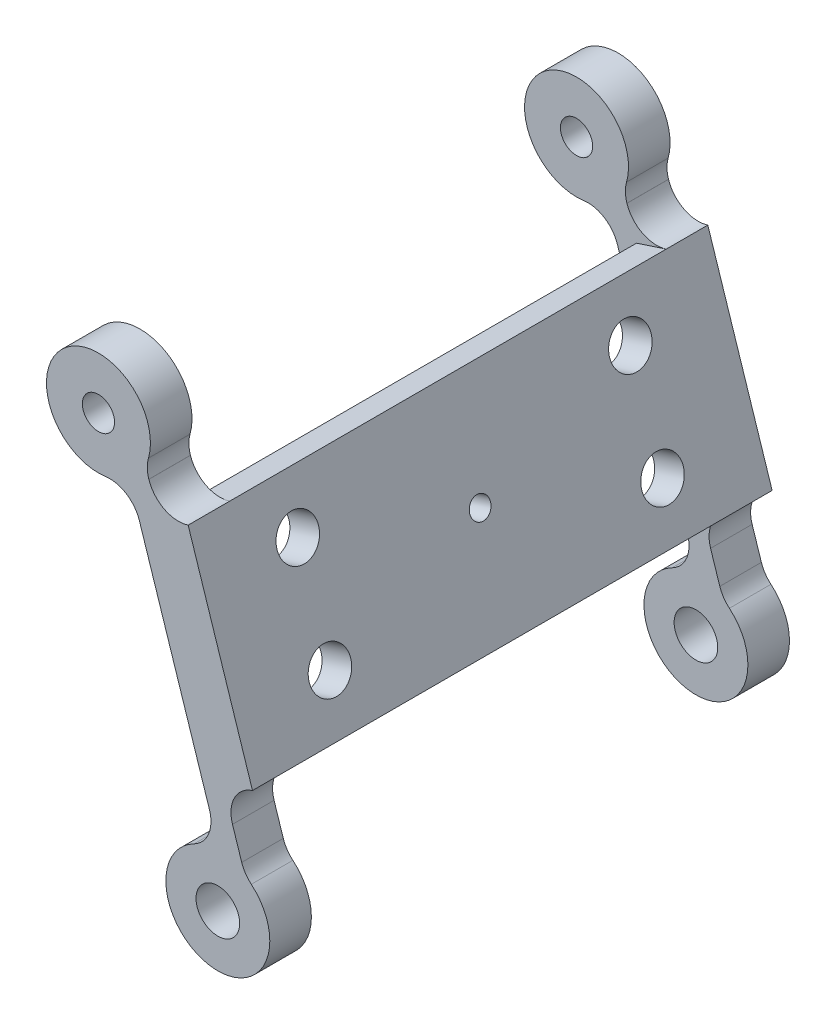
SolidWorks part; units mm, degrees
ref_plane "Front Plane" through (0, 0, 0) normal (0, 0, 1) x (1, 0, 0)
ref_plane "Top Plane" through (0, 0, 0) normal (0, 1, 0) x (1, 0, 0)
ref_plane "Right Plane" through (0, 0, 0) normal (1, 0, 0) x (0, 0, -1)
sketch "Sketch1" plane through (0, 0, 0) normal (0, 0, 1) x (1, 0, 0)
  line L2 (-17.3976, 40.0711) -> (-7.8424, 10.7162)
  line L3 (-10.6381, 12.6112) -> (-10.2569, 11.44)
  line L4 (-18.7542, 37.5449) -> (-10.6381, 12.6112)
  line L5 (-18.7542, 37.5449) -> (-18.9568, 38.1671)
  circle A0 centre (-21.9266, 42.1896) radius 1.55
  arc A2 (-17.3976, 40.0711) -> (-18.9568, 38.1671) centre (-21.9266, 42.1896) ccw
  arc A3 (-10.2569, 11.44) -> (-7.8424, 10.7162) centre (-10.4388, 6.4433) ccw
  circle A5 centre (-10.4388, 6.4433) radius 2.1
extrude "Boss-Extrude1" add sketch "Sketch1" along normal blind 4 contours L2 L4 A0 A5 region at (-13.1006, 25.2372, 0)
sketch "Sketch2" plane through (0, 0, 4) normal (0, 0, 1) x (1, 0, 0)
  line L0 (-16.1484, 36.2334) -> (-9.958, 17.2156)
  line L1 (-16.1484, 36.2334) -> (-13.2958, 37.162)
  line L2 (-9.958, 17.2156) -> (-7.1053, 18.1442)
  line L3 (-13.2958, 37.162) -> (-7.1053, 18.1442)
  line L4 (-17.3976, 40.0711) -> (-7.8424, 10.7162) construction
  dimension "D1" = 3
  dimension "D2" = 20
extrude "Boss-Extrude2" add sketch "Sketch2" against normal blind 50
ref_plane "Plane1" through (0, 0, -21) normal (0, 0, 1) x (1, 0, 0)
mirror "Mirror1" about plane through (0, 0, -21) normal (0, 0, 1) of "Boss-Extrude1"
sketch "Sketch3" plane through (-3.937, -1.2815, 0) normal (-0.9509, -0.3095, 0) x (0, 0, 1)
  line L0 (0, 39.4524) -> (0, 34.4524) construction
  line L1 (0, 34.4524) -> (-5, 34.4524) construction
  line L2 (0, 29.4524) -> (-10.938, 29.4524) construction
  line L3 (0, 39.4524) -> (0, 19.4524) construction
  line L4 (-21, 19.4524) -> (-21, 39.4524) construction
  line L7 (-42, 19.4524) -> (0, 19.4524) construction
  line L8 (-42, 39.4524) -> (0, 39.4524) construction
  circle A0 centre (-5, 34.4524) radius 2
  circle A1 centre (-5, 24.4524) radius 2
  circle A2 centre (-37, 24.4524) radius 2
  circle A3 centre (-37, 34.4524) radius 2
  circle A4 centre (-21, 29.4524) radius 1
extrude "Cut-Extrude1" cut sketch "Sketch3" against normal blind 10
fillet "Fillet1" radius 3 12 edges at (-9.958, 17.2156, 2) (-9.958, 17.2156, -44) (-16.1484, 36.2334, -44) (-16.1484, 36.2334, 2) (-10.2569, 11.44, 2) (-7.8424, 10.7162, 2) (-7.8424, 10.7162, -44) (-10.2569, 11.44, -44) (-18.9568, 38.1671, -44) (-17.3976, 40.0711, -44) (-17.3976, 40.0711, 2) (-18.9568, 38.1671, 2)
ref_plane "Plane2" through (0, 0, -21) normal (0, 0, -1) x (-1, 0, 0)
